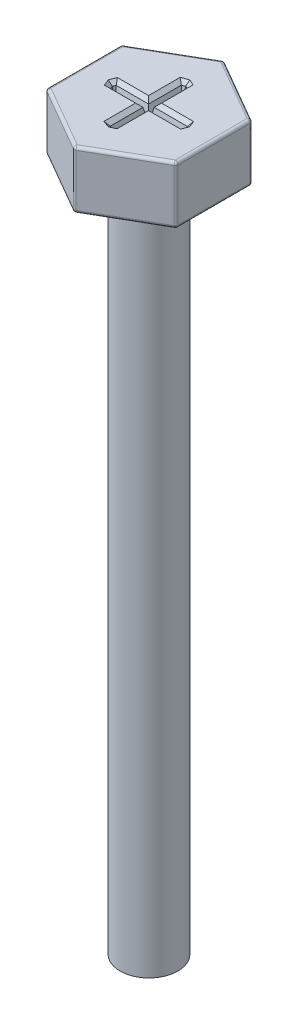
SolidWorks part; units mm, degrees
ref_plane "Front Plane" through (0, 0, 0) normal (0, 0, 1) x (1, 0, 0)
ref_plane "Top Plane" through (0, 0, 0) normal (0, 1, 0) x (1, 0, 0)
ref_plane "Right Plane" through (0, 0, 0) normal (1, 0, 0) x (0, 0, -1)
sketch "Sketch1" plane through (0, 0, 0) normal (0, 1, 0) x (1, 0, 0)
  circle A0 centre (0, 0) radius 2
  dimension "D1" = 4
extrude "Boss-Extrude1" add sketch "Sketch1" against normal blind 47
sketch "Sketch2" plane through (0, 0, 0) normal (0, 1, 0) x (1, 0, 0)
  line L1 (0, 5.1962) -> (-4.5, 2.5981)
  line L2 (-4.5, 2.5981) -> (-4.5, -2.5981)
  line L3 (-4.5, -2.5981) -> (0, -5.1962)
  line L4 (0, -5.1962) -> (4.5, -2.5981)
  line L5 (4.5, -2.5981) -> (4.5, 2.5981)
  line L6 (4.5, 2.5981) -> (0, 5.1962)
  circle A0 centre (0, 0) radius 4.5 construction
  dimension "D1" = 9
extrude "Boss-Extrude2" add sketch "Sketch2" along normal blind 4
fillet "Fillet1" radius 0.2 18 edges at (2.25, 0, -3.8971) (-2.25, 0, -3.8971) (-4.5, 0, 0) (-2.25, 0, 3.8971) (2.25, 0, 3.8971) (4.5, 0, 0) (2.25, 4, -3.8971) (-2.25, 4, -3.8971) (-4.5, 4, 0) (-2.25, 4, 3.8971) (2.25, 4, 3.8971) (4.5, 2, -2.5981) (4.5, 2, 2.5981) (0, 2, 5.1962) (-4.5, 2, 2.5981) (-4.5, 2, -2.5981) (0, 2, -5.1962) (4.5, 4, 0)
sketch "Sketch3" plane through (0, 4, 0) normal (0, 1, 0) x (1, 0, 0)
  line L0 (-7.6409, 0) -> (6.8127, 0) construction
  line L2 (0, 2.6) -> (-0.2805, 2.5)
  line L3 (-0.2805, 2.5) -> (-0.2805, 0.25)
  line L4 (-0.2805, 0.25) -> (-2.5, 0.25)
  line L5 (-2.5, 0.25) -> (-2.6, 0)
  line L6 (2.5, 0.25) -> (2.6, 0)
  line L7 (0.2195, 0.25) -> (2.5, 0.25)
  line L8 (0.2195, 2.5) -> (0.2195, 0.25)
  line L9 (0, 2.6) -> (0.2195, 2.5)
  line L10 (0, -5.537) -> (0, 5.7507) construction
  line L11 (0, -2.6) -> (0.2195, -2.5)
  line L12 (0.2195, -2.5) -> (0.2195, -0.25)
  line L13 (0.2195, -0.25) -> (2.5, -0.25)
  line L14 (2.5, -0.25) -> (2.6, 0)
  line L15 (-2.5, -0.25) -> (-2.6, 0)
  line L16 (-0.2805, -0.25) -> (-2.5, -0.25)
  line L17 (-0.2805, -2.5) -> (-0.2805, -0.25)
  line L18 (0, -2.6) -> (-0.2805, -2.5)
  dimension "D1" = 0.5
  dimension "D2" = 0.5
  dimension "D3" = 0.5
  dimension "D4" = 5
  dimension "D5" = 5
  dimension "D6" = 5.2
  dimension "D7" = 5.2
  dimension "D8" = 0.1
  dimension "D9" = 0.1
  dimension "D10" = 2.6
extrude "Cut-Extrude2" cut sketch "Sketch3" against normal blind 1 draft 12
chamfer "Chamfer1" distance 0.2 angle 45 16 edges at (0.1097, 4, 2.55) (-0.1403, 4, 2.55) (-0.2805, 4, 1.375) (0.2195, 4, 1.375) (1.3597, 4, 0.25) (2.55, 4, 0.125) (2.55, 4, -0.125) (1.3597, 4, -0.25) (0.2195, 4, -1.375) (0.1097, 4, -2.55) (-0.1403, 4, -2.55) (-0.2805, 4, -1.375) (-1.3903, 4, 0.25) (-2.55, 4, 0.125) (-2.55, 4, -0.125) (-1.3903, 4, -0.25) first distance on face at (-0.0153, 4, 0)
